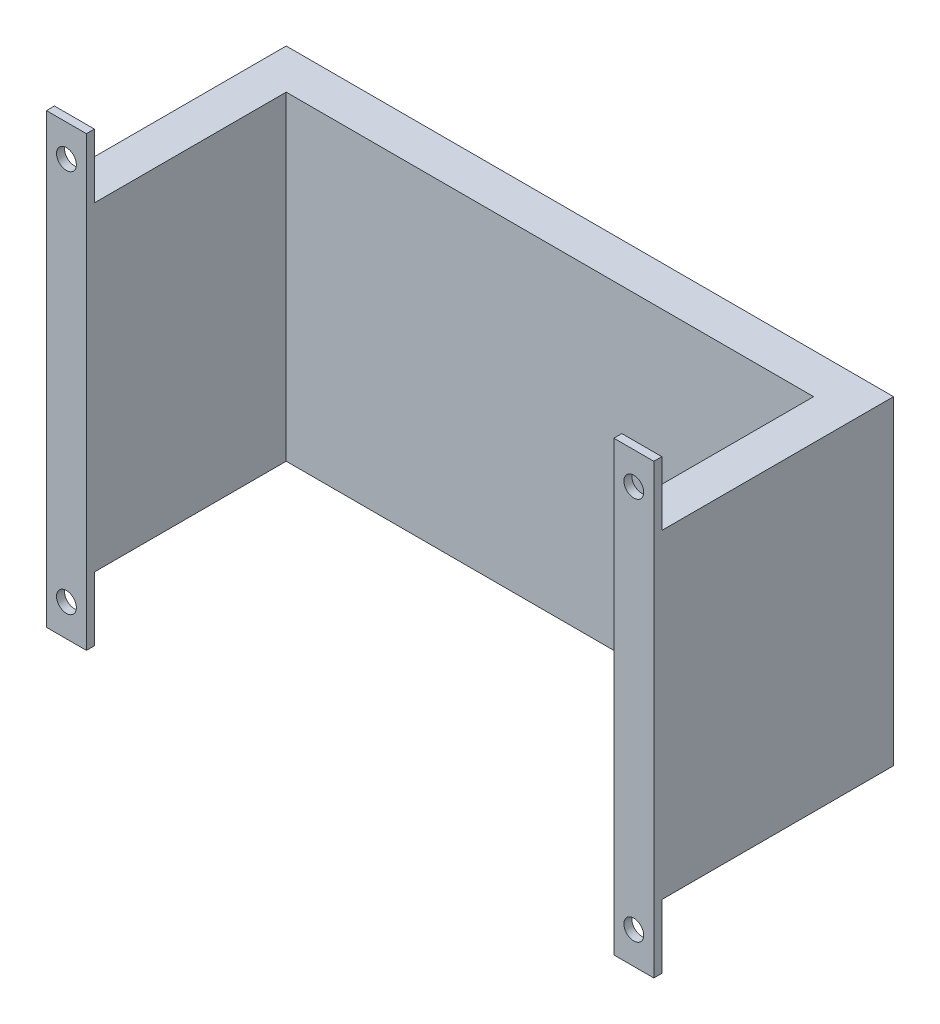
SolidWorks part; units mm, degrees
material "1060 Alloy"
ref_plane "Front Plane" through (0, 0, 0) normal (0, 0, 1) x (1, 0, 0)
ref_plane "Top Plane" through (0, 0, 0) normal (0, 1, 0) x (1, 0, 0)
ref_plane "Right Plane" through (0, 0, 0) normal (1, 0, 0) x (0, 0, -1)
sketch "Sketch1" plane through (0, 0, 0) normal (0, 0, 1) x (1, 0, 0)
  line L1 (120.65, -63.5) -> (-120.65, -63.5)
  line L2 (120.65, -63.5) -> (120.65, 63.5)
  line L3 (120.65, 63.5) -> (-120.65, 63.5)
  line L4 (-120.65, -63.5) -> (-120.65, 63.5)
  line L5 (120.65, -63.5) -> (-120.65, 63.5) construction
  line L6 (120.65, 63.5) -> (-120.65, -63.5) construction
  point P0 (0, 0)
  dimension "D1" = 127
  dimension "D2" = 241.3
extrude "Boss-Extrude1" add sketch "Sketch1" along normal blind 95.25
sketch "Sketch5" plane through (0, 0, 95.25) normal (0, 0, 1) x (1, 0, 0)
  line L1 (104.775, -63.5) -> (-104.775, -63.5)
  line L2 (104.775, -63.5) -> (104.775, 63.5)
  line L3 (104.775, 63.5) -> (-104.775, 63.5)
  line L4 (-104.775, -63.5) -> (-104.775, 63.5)
  line L5 (104.775, -63.5) -> (-104.775, 63.5) construction
  line L6 (104.775, 63.5) -> (-104.775, -63.5) construction
  point P0 (0, 0)
  dimension "D1" = 127
  dimension "D2" = 209.55
extrude "Cut-Extrude1" cut sketch "Sketch5" against normal blind 79.375
sketch "Sketch6" plane through (0, 0, 95.25) normal (0, 0, 1) x (1, 0, 0)
  line L1 (104.775, 88.9) -> (120.65, 88.9)
  line L2 (104.775, 88.9) -> (104.775, 63.5)
  line L3 (104.775, 63.5) -> (120.65, 63.5)
  line L4 (120.65, 88.9) -> (120.65, 63.5)
  line L5 (104.775, 88.9) -> (120.65, 63.5) construction
  line L6 (104.775, 63.5) -> (120.65, 88.9) construction
  line L8 (120.65, 63.5) -> (104.775, 63.5) construction
  line L9 (120.65, -63.5) -> (120.65, 63.5) construction
  line L11 (0, -52.3875) -> (0, 52.3875) construction
  line L12 (-104.775, 63.5) -> (-120.65, 63.5)
  line L13 (-120.65, 88.9) -> (-120.65, 63.5)
  line L14 (-104.775, 88.9) -> (-120.65, 88.9)
  line L15 (-104.775, 88.9) -> (-104.775, 63.5)
  line L16 (52.3875, 0) -> (-52.3875, 0) construction
  line L17 (104.775, -63.5) -> (120.65, -63.5)
  line L18 (120.65, -88.9) -> (120.65, -63.5)
  line L19 (104.775, -88.9) -> (120.65, -88.9)
  line L20 (104.775, -88.9) -> (104.775, -63.5)
  line L21 (-104.775, -88.9) -> (-104.775, -63.5)
  line L22 (-104.775, -88.9) -> (-120.65, -88.9)
  line L23 (-120.65, -88.9) -> (-120.65, -63.5)
  line L24 (-104.775, -63.5) -> (-120.65, -63.5)
  point P0 (112.7125, 76.2)
  dimension "D1" = 15.875
  dimension "D4" = 25.4
extrude "Boss-Extrude2" add sketch "Sketch6" against normal blind 3.175
sketch "Sketch7" plane through (0, 0, 92.075) normal (0, 0, -1) x (-1, 0, 0)
  line L0 (112.7125, 88.9) -> (112.7125, 63.5) construction
  line L1 (104.775, 88.9) -> (120.65, 88.9) construction
  line L2 (120.65, 63.5) -> (104.775, 63.5) construction
  line L3 (104.775, 76.2) -> (120.65, 76.2) construction
  line L4 (104.775, 63.5) -> (104.775, 88.9) construction
  line L5 (120.65, 88.9) -> (120.65, 63.5) construction
  line L6 (0, 52.3875) -> (0, -52.3875) construction
  line L7 (52.3875, 0) -> (-52.3875, 0) construction
  circle A0 centre (112.7125, 76.2) radius 3.937
  circle A1 centre (-112.7125, 76.2) radius 3.937
  circle A2 centre (112.7125, -76.2) radius 3.937
  circle A3 centre (-112.7125, -76.2) radius 3.937
  dimension "D1" = 7.874
extrude "Cut-Extrude2" cut sketch "Sketch7" against normal through all
equation "\"Height\"= 5"
equation "\"D1@Sketch1\"=\"Height\""
equation "\"D1@Sketch5\"=\"Height\""
